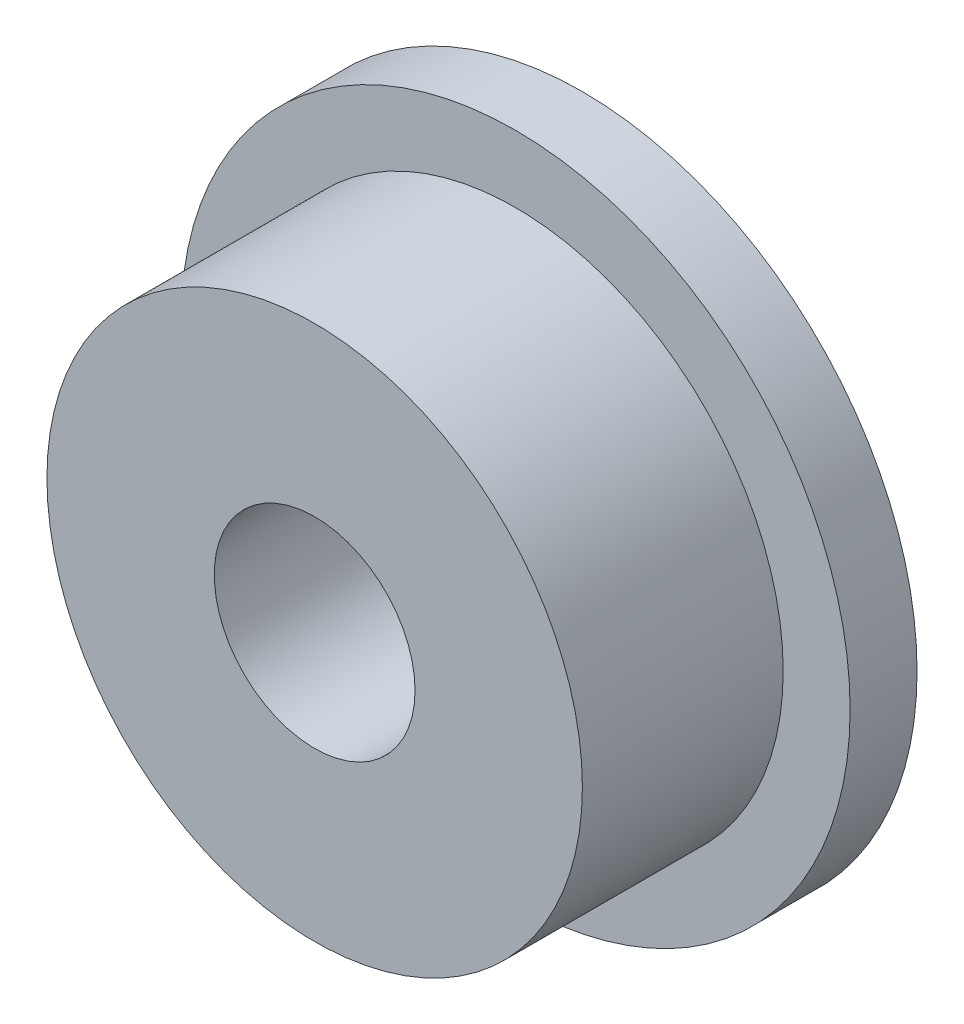
SolidWorks part; units mm, degrees
ref_plane "Front Plane" through (0, 0, 0) normal (0, 0, 1) x (1, 0, 0)
ref_plane "Top Plane" through (0, 0, 0) normal (0, 1, 0) x (1, 0, 0)
ref_plane "Right Plane" through (0, 0, 0) normal (1, 0, 0) x (0, 0, -1)
sketch "草图1" plane through (0, 0, 0) normal (0, 0, 1) x (1, 0, 0)
  circle A0 centre (0, 0) radius 1.5
  circle A1 centre (0, 0) radius 4
  circle A2 centre (0, 0) radius 5
  dimension "D1" = 3
  dimension "D2" = 8
  dimension "D3" = 10
extrude "凸台-拉伸1" add sketch "草图1" along normal blind 4 contours A0 | A1
extrude "凸台-拉伸3" add sketch "草图1<4>" along normal blind 1 contours A0 | A2
sketch "草图1<4>" plane through (0, 0, 0) normal (0, 0, 1) x (1, 0, 0) same geometry as "草图1"
